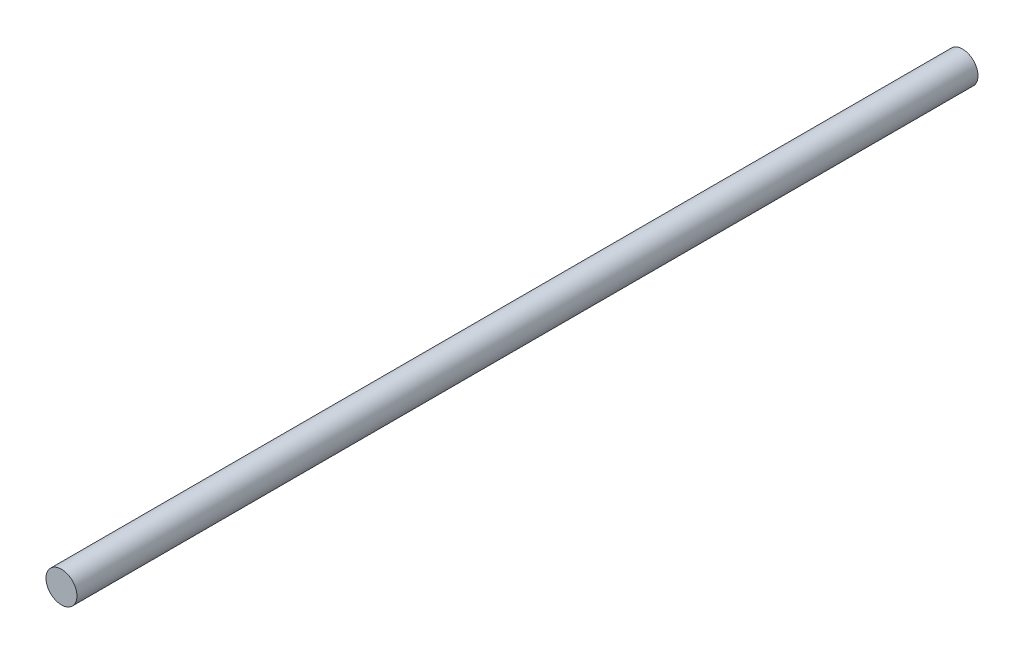
SolidWorks part; units mm, degrees
ref_plane "Alzado" through (0, 0, 0) normal (0, 0, 1) x (1, 0, 0)
ref_plane "Planta" through (0, 0, 0) normal (0, 1, 0) x (1, 0, 0)
ref_plane "Vista lateral" through (0, 0, 0) normal (1, 0, 0) x (0, 0, -1)
sketch "Croquis1" plane through (0, 0, 0) normal (0, 0, 1) x (1, 0, 0)
  circle A0 centre (0, 0) radius 6
  dimension "D1" = 12
extrude "Saliente-Extruir1" add sketch "Croquis1" along normal blind 349.2
